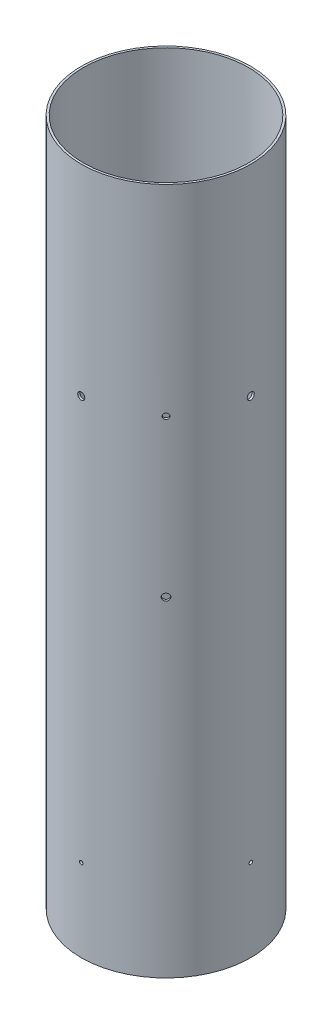
SolidWorks part; units mm, degrees
ref_plane "Front Plane" through (0, 0, 0) normal (0, 0, 1) x (1, 0, 0)
ref_plane "Top Plane" through (0, 0, 0) normal (0, 1, 0) x (1, 0, 0)
ref_plane "Right Plane" through (0, 0, 0) normal (1, 0, 0) x (0, 0, -1)
sketch "Sketch2" plane through (0, 0, 0) normal (0, 1, 0) x (1, 0, 0)
  circle A0 centre (0, 0) radius 76.3651
  circle A1 centre (0, 0) radius 78.359
  dimension "D1" = 152.7302
  dimension "D2" = 156.718
extrude "Boss-Extrude1" add sketch "Sketch2" along normal blind 635
ref_plane "Plane1" through (55.4082, 0, 55.4082) normal (0.7071, 0, 0.7071) x (0, -1, 0)
sketch "Sketch4" plane through (0, 0, 0) normal (0, 0, 1) x (1, 0, 0)
  circle A0 centre (0, 449.5038) radius 3.2639
  dimension "D2" = 6.5278
  dimension "D1" = 449.5038
extrude "Cut-Extrude2" cut sketch "Sketch4" against normal through all both and the other way through all
pattern_circular "CirPattern2" count 4 over 360 about axis through (0, 635, 0) along (0, 1, 0) of "Cut-Extrude2"
sketch "Sketch5" plane through (55.4082, 0, 55.4082) normal (0.7071, 0, 0.7071) x (0, -1, 0)
  circle A0 centre (-449.5038, 0) radius 2.5794
  dimension "D1" = 5.1587
  dimension "D2" = 449.5038
extrude "Cut-Extrude3" cut sketch "Sketch5" against normal up to surface and the other way through all up to face at (-76.299, 448.7564, 3.1772)
sketch "Sketch6" plane through (189.1754, 0, -78.359) normal (-0.7071, 0, -0.7071) x (-0.7071, 0, 0.7071)
  circle A0 centre (189.1754, 304.8) radius 3.175
  dimension "D2" = 304.8
extrude "Vent Hole" cut sketch "Sketch6" along normal up to surface (2.0599 mm away) up to face at (52.1938, 448.9122, 55.7444)
ref_plane "Plane2" through (0, 0, 78.359) normal (0, 0, 1) x (1, 0, 0)
sketch "Sketch7" plane through (0, 0, 78.359) normal (0, 0, 1) x (1, 0, 0)
  point P0 (0, 76.2)
  dimension "D1" = 76.2
hole_wizard "#4 Clearance Hole1" positions "Sketch7" profile "Sketch8" hole size "#4" standard "ANSI Inch" end condition through all
sketch "Sketch8" plane through (0, 76.2, 78.359) normal (1, 0, 0) x (0, -1, 0)
  line L0 (0, 0) -> (0, 156.718)
  line L1 (0, 156.718) -> (1.6319, 156.718)
  line L2 (1.6319, 156.718) -> (1.6319, 0)
  line L5 (1.6319, 0) -> (0, 0)
  line L11 (0, -6.35) -> (0, 107.95) construction
  dimension "Thru Hole Dia." = 3.2639
  dimension "Thru Hole Depth" = 156.718
pattern_circular "CirPattern3" count 2 every 90 about axis through (0, 0, 0) along (0, 1, 0) of "#4 Clearance Hole1"
equation "\"Shear Pin Dia\"= 3 / 32"
equation "\"Shear Pin Offset\"= 3"
equation "\"Bulkhead Screw Dia\" = 0.257"
equation "\"Bulkhead Screw Offset\"= 17.697"
equation "\"D1@Sketch4\"=\"Bulkhead Screw Offset\""
equation "\"D2@Sketch4\"=\"Bulkhead Screw Dia\""
equation "\"Rail Button Offset\"= 17.697"
equation "\"Rail Button Dia\"=0.2031"
equation "\"D1@Sketch5\"=\"Rail Button Dia\""
equation "\"Vent Hole Dia\"= 0.25"
equation "\"Vent Hole Offset\"= 12"
equation "\"D2@Sketch6\"=\"Vent Hole Offset\""
equation "\"D1@Sketch7\"=\"Shear Pin Offset\""
